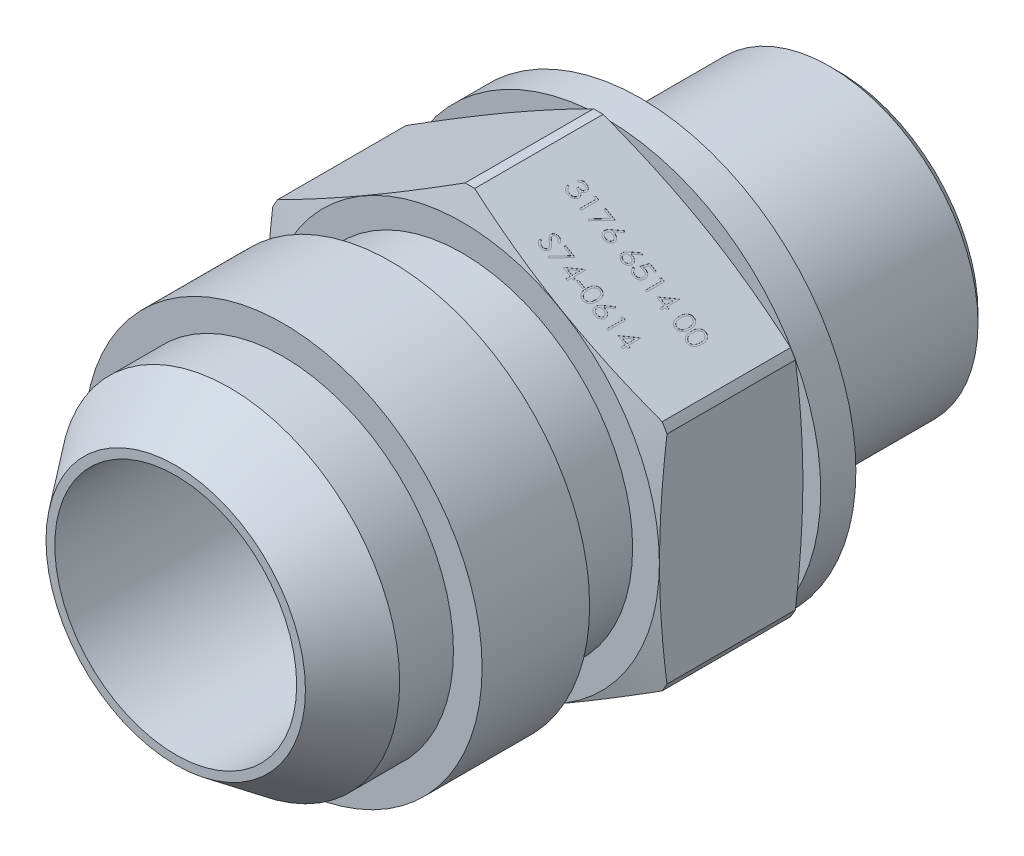
SolidWorks part; units mm, degrees
material "4140 H/T"
ref_plane "Front Plane" through (0, 0, 0) normal (0, 0, 1) x (1, 0, 0)
ref_plane "Top Plane" through (0, 0, 0) normal (0, 1, 0) x (1, 0, 0)
ref_plane "Right Plane" through (0, 0, 0) normal (1, 0, 0) x (0, 0, -1)
sketch "Sketch1" plane through (0, 0, 0) normal (1, 0, 0) x (0, 0, -1)
  line L0 (0, 0) -> (90.3331, 0) construction
  line L1 (0, 7.2393) -> (3, 9.5)
  line L2 (3, 9.5) -> (6, 9.5)
  line L3 (6, 9.5) -> (6, 11.1)
  line L4 (6, 11.1) -> (12, 11.1)
  line L5 (12, 11.1) -> (12, 9.5)
  line L6 (12, 9.5) -> (16, 9.5)
  line L7 (16, 9.5) -> (16, 10.994)
  line L8 (16.4169, 12.55) -> (23.5831, 12.55)
  line L9 (24, 10.994) -> (24, 8.275)
  line L10 (24, 8.275) -> (36.5, 8.275)
  line L11 (37, 7.775) -> (37, 6.8)
  line L12 (37, 6.8) -> (33.3627, 4.7)
  line L13 (33.3627, 4.7) -> (11.2318, 4.7)
  line L14 (0, 6.75) -> (0, 7.2393)
  line L15 (36.5, 8.275) -> (37, 7.775)
  line L16 (16.4169, 12.55) -> (16, 10.994)
  line L17 (23.5831, 12.55) -> (24, 10.994)
  line L18 (0, 6.75) -> (10, 6.75)
  line L19 (10, 6.75) -> (11.2318, 4.7)
  point P14 (37, 8.275)
  dimension "D1" = 25.1
  dimension "D2" = 16.55
  dimension "D3" = 9.4
  dimension "D4" = 13.6
  dimension "D5" = 30
  dimension "D6" = 13
  dimension "D7" = 8
  dimension "D8" = 4
  dimension "D9" = 3
  dimension "D10" = 19
  dimension "D11" = 22.2
  dimension "D12" = 37
  dimension "D13" = 3
  dimension "D14" = 37
  dimension "D15" = 15
  dimension "D16" = 15
  dimension "D18" = 1.556
  dimension "D19" = 59
  dimension "D20" = 13.5
  dimension "D21" = 10
revolve "Revolve1" add sketch "Sketch1" angle 360 about L0
cosmetic thread "Cosmetic Thread1" parameters "D2"=20.3
cosmetic thread "Cosmetic Thread2" parameters "D2"=15.55
sketch "Sketch2" plane through (0, 0, -16) normal (0, 0, 1) x (1, 0, 0)
  line L1 (0, 12.7017) -> (-11, 6.3509)
  line L2 (-11, 6.3509) -> (-11, -6.3509)
  line L3 (-11, -6.3509) -> (0, -12.7017)
  line L4 (0, -12.7017) -> (11, -6.3509)
  line L5 (11, -6.3509) -> (11, 6.3509)
  line L6 (11, 6.3509) -> (0, 12.7017)
  circle A0 centre (0, 0) radius 11 construction
  dimension "D1" = 22
extrude "Extrude2" cut sketch "Sketch2" against normal up to surface (8 mm away) flip side to cut up to face at (10.994, 0, -24)
sketch "Sketch3" plane through (0, 0, -24) normal (0, 0, -1) x (-1, 0, 0)
  circle A0 centre (0, 0) radius 12
  dimension "D1" = 24
extrude "Extrude3" add sketch "Sketch3" along normal blind 1.96
sketch "Sketch4" plane through (0, 0, -25.96) normal (0, 0, -1) x (-1, 0, 0)
  circle A0 centre (0, 0) radius 4.7
  circle A1 centre (0, 0) radius 4.7 construction
extrude "Extrude4" cut sketch "Sketch4" against normal through all
sketch "Sketch5" plane through (5.5, 9.5263, 0) normal (0.5, 0.866, 0) x (0.866, -0.5, 0)
  line L0 (-5.719, 19.8) -> (5.5838, 19.8) construction
  line L1 (-10.994, 24) -> (10.994, 24) construction
  text T0 "3176 6514 00\r\nS74-0614\r\n" font "Century Gothic" height 1
  dimension "D1" = 4.2
extrude "Cut-Extrude1" cut sketch "Sketch5" against normal blind 0.01
